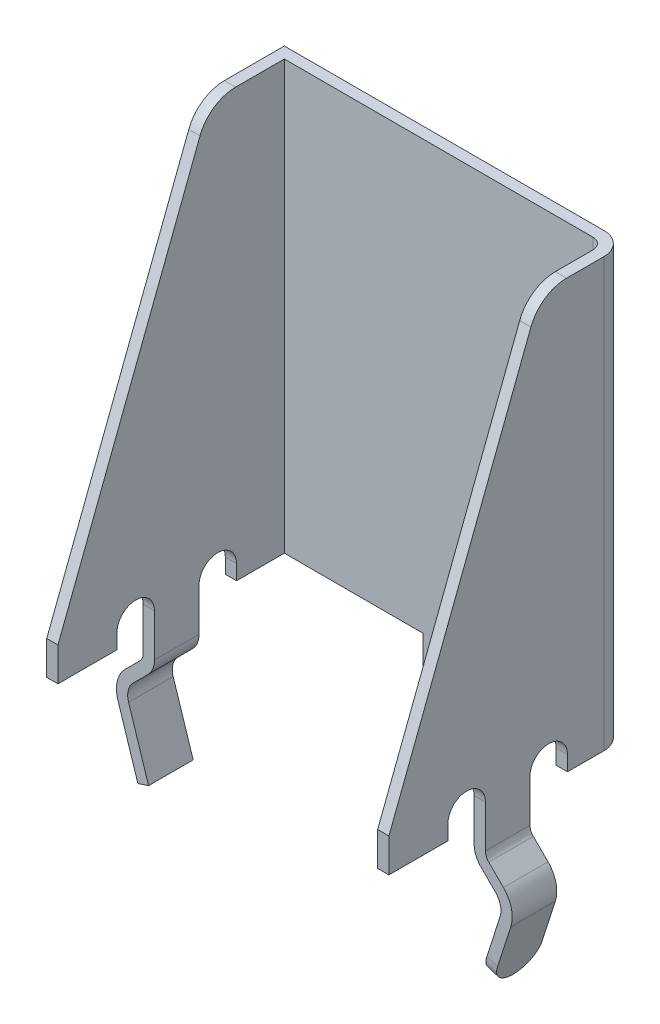
SolidWorks part; units mm, degrees
ref_plane "Front Plane" through (0, 0, 0) normal (0, 0, 1) x (1, 0, 0)
ref_plane "Top Plane" through (0, 0, 0) normal (0, 1, 0) x (1, 0, 0)
ref_plane "Right Plane" through (0, 0, 0) normal (1, 0, 0) x (0, 0, -1)
sketch "Sketch1" plane through (0, 0, 0) normal (0, 1, 0) x (1, 0, 0)
  line L1 (4.565, 0.15) -> (-4.565, 0.15)
  line L2 (4.565, 0.15) -> (4.565, -0.15)
  line L3 (4.565, -0.15) -> (-4.565, -0.15)
  line L4 (-4.565, 0.15) -> (-4.565, -0.15)
  line L5 (4.565, 0.15) -> (-4.565, -0.15) construction
  line L6 (4.565, -0.15) -> (-4.565, 0.15) construction
  point P0 (0, 0)
  dimension "D1" = 0.3
  dimension "D2" = 9.13
extrude "Boss-Extrude1" add sketch "Sketch1" along normal blind 11.42
sketch "Sketch3" plane through (0, 0, -0.15) normal (0, 0, -1) x (-1, 0, 0)
  line L0 (-0.57, 0) -> (0.57, 0)
  line L1 (-4.565, 0) -> (4.565, 0) construction
  line L2 (0.57, 0) -> (0.57, -1.6)
  line L3 (0.57, -1.6) -> (0.33, -2.7708)
  line L4 (-0.57, 0) -> (-0.57, -1.6)
  line L5 (-0.57, -1.6) -> (-0.33, -2.7708)
  arc A0 (-0.33, -2.7708) -> (0.33, -2.7708) centre (0, -2.7031) ccw
  point P6 (0, 0)
  point P12 (0, -3.04)
  dimension "D1" = 1.14
  dimension "D2" = 3.04
  dimension "D3" = 1.6
  dimension "D4" = 0.66
extrude "Boss-Extrude3" add sketch "Sketch3" against normal up to surface (0.3 mm away) up to face at (0, 5.71, 0.15)
sketch "Sketch4" plane through (4.565, 0, 0) normal (1, 0, 0) x (0, 0, -1)
  line L0 (-0.15, 11.42) -> (-0.15, 0)
  line L1 (-0.15, 0) -> (-1.425, 0)
  line L2 (-0.15, 11.42) -> (-1.45, 11.42)
  line L3 (-2.4, 10.7672) -> (-6.19, 0.9)
  line L4 (-6.19, 0.9) -> (-6.19, 0)
  line L5 (-3.615, 0) -> (-2.425, 0)
  line L6 (-1.425, 0) -> (-1.425, 0.4)
  line L7 (-2.425, 0.4) -> (-2.425, 0)
  line L8 (-3.615, 0) -> (-3.615, 0.4)
  line L9 (-4.615, 0.4) -> (-4.615, 0)
  line L10 (-4.615, 0) -> (-6.19, 0)
  line L11 (0.15, 11.42) -> (0.15, 0) construction
  arc A0 (-1.45, 11.42) -> (-2.4, 10.7672) centre (-1.45, 10.4023) ccw
  arc A1 (-1.425, 0.4) -> (-2.425, 0.4) centre (-1.925, 0.4) ccw
  arc A2 (-3.615, 0.4) -> (-4.615, 0.4) centre (-4.115, 0.4) ccw
  point P9 (-3.02, 0)
  point P28 (-4.115, 0.9)
  dimension "D1" = 3.17
  dimension "D3" = 1
  dimension "D5" = 6.34
  dimension "D2" = 1.19
  dimension "D4" = 0.4
  dimension "D6" = 1.3
  dimension "D7" = 2.25
extrude "Boss-Extrude4" add sketch "Sketch4" against normal blind 0.3
fillet "Fillet2" radius 0.3 1 edges at (4.265, 5.71, 0.15)
fillet "Fillet3" radius 0.6 1 edges at (4.565, 5.71, -0.15)
ref_plane "Plane1" through (0, 0, 3.02) normal (0, 0, -1) x (-1, 0, 0)
sketch "Sketch5" plane through (0, 0, 3.02) normal (0, 0, -1) x (-1, 0, 0)
  line L0 (-4.565, 0) -> (-4.265, 0)
  line L1 (-4.565, 0) -> (-4.565, -0.7344)
  line L2 (-4.265, 0) -> (-4.265, -0.7344)
  line L3 (-4.6529, -0.9465) -> (-5.0457, -1.3393)
  line L4 (-4.4407, -1.1586) -> (-4.8336, -1.5514)
  line L5 (-5.2416, -2.1499) -> (-4.7078, -3.81)
  line L6 (-4.7078, -3.81) -> (-4.4222, -3.7182)
  line L7 (-4.4222, -3.7182) -> (-4.956, -2.0581)
  line L8 (-5.28, -1.8087) -> (-5.28, -4.8094) construction
  arc A0 (-4.565, -0.7344) -> (-4.6529, -0.9465) centre (-4.865, -0.7344) cw
  arc A1 (-4.265, -0.7344) -> (-4.4407, -1.1586) centre (-4.865, -0.7344) cw
  arc A2 (-4.8336, -1.5514) -> (-4.956, -2.0581) centre (-4.48, -1.905) ccw
  arc A3 (-5.0457, -1.3393) -> (-5.2416, -2.1499) centre (-4.48, -1.905) ccw
  point P23 (-4.565, -3.7641)
  dimension "D1" = 5.28
  dimension "D4" = 0.5
  dimension "D5" = 0.3
  dimension "D2" = 3.81
  dimension "D3" = 1.905
  dimension "D6" = 45
extrude "Boss-Extrude5" add sketch "Sketch5" along normal up to surface and the other way up to surface up to face at (4.415, 0.2, 2.425) other way up to face at (4.415, 0.2, 3.615)
fillet "Fillet4" radius 0.595 2 edges at (4.565, -3.7641, 3.615) (4.565, -3.7641, 2.425)
mirror "Mirror1" about plane through (0, 0, 0) normal (1, 0, 0) of "Boss-Extrude5", "Boss-Extrude4"
sketch "Sketch6" plane through (0, 0, -0.15) normal (0, 0, -1) x (-1, 0, 0)
  line L0 (0, 10.165) -> (0, 9.21)
  line L1 (-3.965, 0) -> (-0.57, 0) construction
  circle A0 centre (0, 6.99) radius 2.22 construction
  circle A1 centre (0, 6.99) radius 3.175 construction
  circle A2 centre (0, 6.99) radius 2.6975
  point P7 (0, 9.6875)
  dimension "D1" = 4.44
  dimension "D2" = 6.35
  dimension "D3" = 6.99
sketch "Sketch7" plane through (0, 0, 0) normal (1, 0, 0) x (0, 0, -1)
  line L0 (0.15, 9.21) -> (0.4365, 9.4741)
  line L1 (0.4365, 9.9009) -> (0.15, 10.165)
  line L2 (0.15, 10.165) -> (0.15, 9.21) construction
  line L3 (0.15, 9.21) -> (0.15, 10.165)
  arc A0 (0.4365, 9.9009) -> (0.4365, 9.4741) centre (0.2398, 9.6875) cw
  point P2 (0, 0)
  point P6 (0, 0)
  point P7 (0.2069, 10.2015)
  point P12 (0.424, 10.0909)
  point P13 (0.53, 9.6875)
  point P14 (0.4384, 9.8974)
  point P15 (0.461, 9.8541)
  point P16 (0.4784, 9.8173)
  point P17 (0.4365, 9.9009)
  dimension "D1" = 0.38
sketch "Sketch11" plane through (0, 0, 0) normal (1, 0, 0) x (0, 0, -1)
  line L0 (0.15, 6.99) -> (4.7338, 6.99) construction
revolve "Revolve2" add sketch "Sketch7" angle 360 about L0
